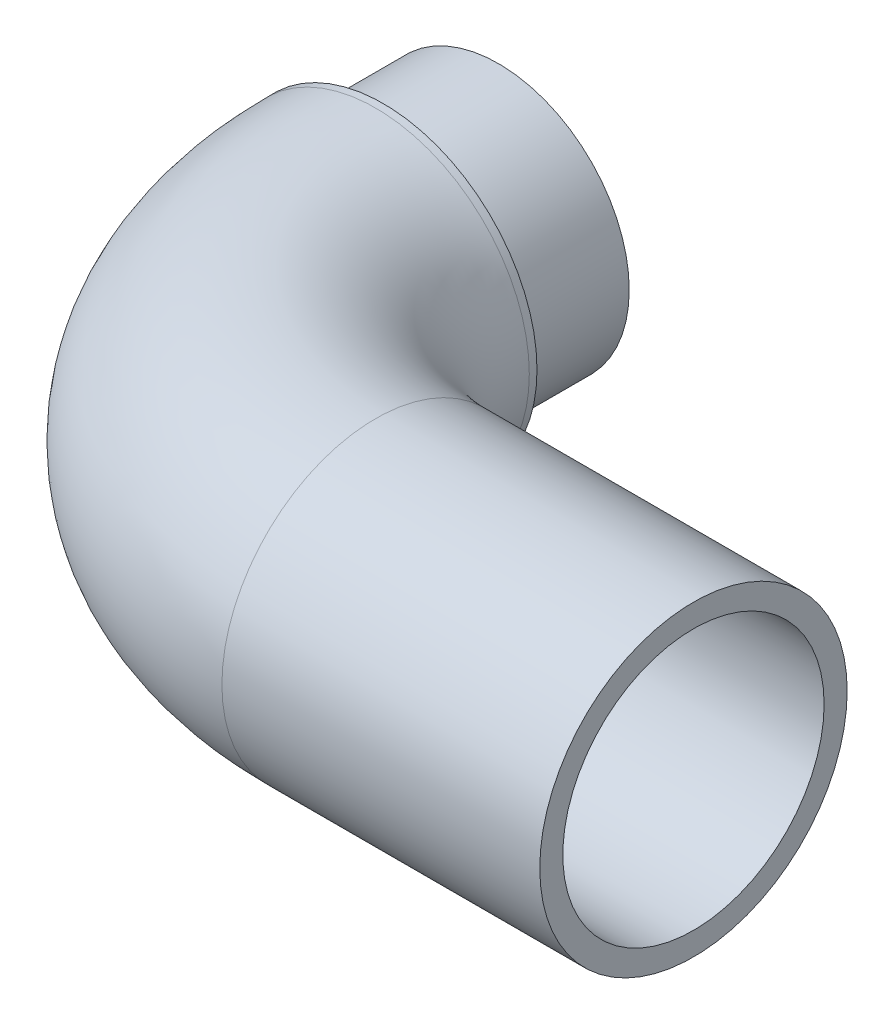
SolidWorks part; units mm, degrees
ref_plane "Front Plane" through (0, 0, 0) normal (0, 0, 1) x (1, 0, 0)
ref_plane "Top Plane" through (0, 0, 0) normal (0, 1, 0) x (1, 0, 0)
ref_plane "Right Plane" through (0, 0, 0) normal (1, 0, 0) x (0, 0, -1)
sketch "Sketch1" plane through (0, 0, 0) normal (0, 0, 1) x (1, 0, 0)
  circle A0 centre (0, 0) radius 17
  dimension "D1" = 34
extrude "Boss-Extrude1" add sketch "Sketch1" along normal blind 15
sketch "Sketch2" plane through (0, 0, 15) normal (0, 0, 1) x (1, 0, 0)
  circle A0 centre (0, 0) radius 20
  dimension "D1" = 40
sketch "Sketch3" plane through (0, 0, 0) normal (0, 1, 0) x (1, 0, 0)
  line L0 (0, -15) -> (0, -16)
  line L1 (-20, -15) -> (20, -15) construction
  line L2 (35, -51) -> (76.3607, -51)
  arc A0 (35, -51) -> (0, -16) centre (35, -16) cw
  point P9 (0, -51)
  dimension "D2" = 35
  dimension "D1" = 36
sweep "Sweep1" add profiles "Sketch2" path "Sketch3"
shell "Shell1" thickness 3 removed face at (76.3607, 0, 31)
